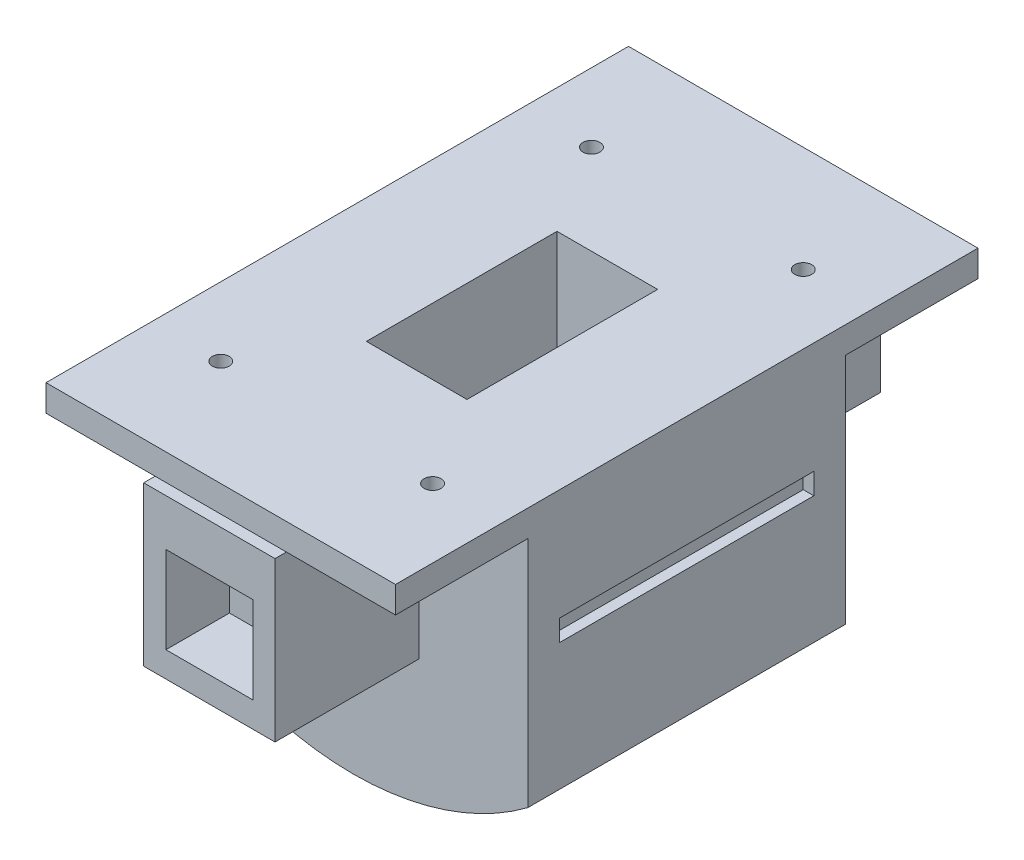
SolidWorks part; units mm, degrees
ref_plane "Front Plane" through (0, 0, 0) normal (0, 0, 1) x (1, 0, 0)
ref_plane "Top Plane" through (0, 0, 0) normal (0, 1, 0) x (1, 0, 0)
ref_plane "Right Plane" through (0, 0, 0) normal (1, 0, 0) x (0, 0, -1)
sketch "Sketch1" plane through (0, 0, 0) normal (0, 0, 1) x (1, 0, 0)
  line L0 (0, 0) -> (0, -42) construction
  line L1 (0, 0) -> (55, 0)
  line L2 (55, 0) -> (-55, 0)
  arc A0 (-55, 0) -> (55, 0) centre (0, 0) ccw
  dimension "D2" = 55
  dimension "D1" = 42
extrude "Boss-Extrude1" add sketch "Sketch1" along normal blind 30 and the other way blind 30 contours L2 A0 L1 region at (0, -23.3427, 0)
sketch "Sketch2" plane through (0, 0, 0) normal (0, 0, 1) x (1, 0, 0)
  line L1 (0, 0) -> (-9.5, 0)
  line L3 (2.8861, -52) -> (-9.5, -52)
  line L4 (-9.5, 0) -> (-9.5, -52)
  line L5 (0, 0) -> (9.5, 0)
  line L7 (2.8861, -52) -> (9.5, -52)
  line L8 (9.5, 0) -> (9.5, -52)
  circle A0 centre (0, 0) radius 42
  dimension "D1" = 84
  dimension "D2" = 9.5
  dimension "D3" = 9.5
  dimension "D4" = 52
extrude "Cut-Extrude1" cut sketch "Sketch2" against normal blind 18 and the other way blind 18 contours L4 A0 L8 L5 L1 | A0 L4 L3 | A0 L3 L7 L8 region at (0, -20.8208, 0) region at (0, -46.8145, 0)
sketch "Sketch3" plane through (0, 0, 30) normal (0, 0, 1) x (1, 0, 0)
  line L0 (0, 0) -> (0, -28.5435) construction
  line L1 (-54.8544, -4) -> (-33, -4)
  line L2 (-54.8544, -4) -> (-54.8544, -49)
  line L3 (-54.8544, -49) -> (-33, -49)
  line L4 (-33, -4) -> (-33, -49)
  line L5 (55, 0) -> (-55, 0) construction
  line L6 (33, -4) -> (33, -49)
  line L7 (54.8544, -49) -> (33, -49)
  line L8 (54.8544, -4) -> (54.8544, -49)
  line L9 (54.8544, -4) -> (33, -4)
  arc A0 (-55, 0) -> (55, 0) centre (0, 0) ccw construction
  dimension "D1" = 4
  dimension "D2" = 33
  dimension "D3" = 45
extrude "Cut-Extrude2" cut sketch "Sketch3" against normal through all
sketch "Sketch4" plane through (0, 0, 0) normal (0, 1, 0) x (1, 0, 0)
  line L0 (55, 30) -> (-55, 30) construction
  line L1 (55, 30) -> (55, -30) construction
  line L2 (0, 0) -> (0, 55.9923) construction
  line L3 (0, 0) -> (36.0907, 0) construction
  circle A0 centre (45, 20) radius 1.6
  circle A1 centre (45, -20) radius 1.6
  circle A2 centre (-45, -20) radius 1.6
  circle A3 centre (-45, 20) radius 1.6
  dimension "D1" = 3.2
  dimension "D2" = 10
  dimension "D3" = 10
extrude "Cut-Extrude3" cut sketch "Sketch4" against normal through all
sketch "Sketch6" plane through (33, 0, 0) normal (1, 0, 0) x (0, 0, -1)
  line L0 (-30, -4) -> (-30, -44) construction
  line L1 (-24, -16) -> (24, -16)
  line L2 (-24, -16) -> (-24, -20)
  line L3 (-24, -20) -> (24, -20)
  line L4 (24, -16) -> (24, -20)
  line L5 (30, -4) -> (30, -44) construction
  line L6 (30, -4) -> (-30, -4) construction
  dimension "D1" = 6
  dimension "D2" = 6
  dimension "D3" = 12
  dimension "D4" = 4
extrude "Cut-Extrude5" cut sketch "Sketch6" against normal blind 2
sketch "Sketch9" plane through (0, 0, 0) normal (0, 1, 0) x (1, 0, 0)
  line L5 (-55, 30) -> (-33, 30)
  line L6 (-55, 30) -> (-55, -30)
  line L7 (-55, -30) -> (-33, -30)
  line L8 (-33, 30) -> (-33, -30)
  line L9 (55, 30) -> (33, 30)
  line L10 (55, 30) -> (55, -30)
  line L11 (55, -30) -> (33, -30)
  line L12 (33, 30) -> (33, -30)
extrude "Cut-Extrude7" cut sketch "Sketch9" against normal through all
sketch "Sketch10" plane through (0, 0, 0) normal (0, 1, 0) x (1, 0, 0)
  line L1 (-33, 30) -> (33, 30)
  line L2 (-33, 30) -> (-33, -30)
  line L3 (-33, -30) -> (33, -30)
  line L4 (33, 30) -> (33, -30)
  line L5 (33, -30) -> (-33, -30)
  line L6 (33, -30) -> (33, -55)
  line L7 (33, -55) -> (-33, -55)
  line L8 (-33, -30) -> (-33, -55)
  line L9 (-33, 30) -> (33, 30)
  line L10 (-33, 30) -> (-33, 55)
  line L11 (-33, 55) -> (33, 55)
  line L12 (33, 30) -> (33, 55)
  line L13 (-9.5, 18) -> (9.5, 18)
  line L14 (-9.5, 18) -> (-9.5, -18)
  line L15 (-9.5, -18) -> (9.5, -18)
  line L16 (9.5, 18) -> (9.5, -18)
  line M3 (-33, 30) -> (-33, -30)
  line M4 (-33, -30) -> (33, -30)
  line M5 (33, -30) -> (33, 30)
  line M6 (33, 30) -> (-33, 30)
  line M7 (9.5, -18) -> (-9.5, -18)
  line M8 (-9.5, -18) -> (-9.5, 18)
  line M9 (-9.5, 18) -> (9.5, 18)
  line M10 (9.5, 18) -> (9.5, -18)
  dimension "D1" = 25
  dimension "D2" = 25
extrude "Boss-Extrude2" add sketch "Sketch10" along normal blind 5 contours L12 L11 L10 M6 | M6 M3 M4 M5 M10 M7 M8 M9 | L8 L7 L6 M4 region at (0, 0, -42.5) region at (0, 0, -29.108) region at (0, 0, 42.5)
sketch "Sketch11" plane through (0, 5, 0) normal (0, 1, 0) x (1, 0, 0)
  line L0 (0, 0) -> (-22.9202, 0) construction
  line L1 (-22.9202, 0) -> (0, 0) construction
  circle A0 centre (-20, 35) radius 1.6
  circle A1 centre (20, 35) radius 1.6
  circle A2 centre (-20, -35) radius 1.6
  circle A3 centre (20, -35) radius 1.6
  dimension "D1" = 3.2
  dimension "D2" = 35
  dimension "D3" = 20
  dimension "D5" = 40
  dimension "D4" = 2
extrude "Cut-Extrude8" cut sketch "Sketch11" against normal through all
sketch "Sketch13" plane through (0, 0, -30) normal (0, 0, -1) x (-1, 0, 0)
  line L0 (33, 0) -> (-33, 0) construction
  line L11 (-18.4, 0) -> (-18.4, 5) construction
  line L12 (-12.4, 0) -> (12.4, 0)
  line L13 (-12.4, 0) -> (-12.4, -30)
  line L14 (-12.4, -30) -> (12.4, -30)
  line L15 (12.4, 0) -> (12.4, -30)
  line L16 (18.4, 5) -> (18.4, 0) construction
  point P0 (0, -17)
  dimension "D5" = 6
  dimension "D6" = 30
  dimension "D7" = 6
extrude "Boss-Extrude3" add sketch "Sketch13" along normal blind 27.15
sketch "Sketch14" plane through (0, 0, -57.15) normal (0, 0, -1) x (-1, 0, 0)
  line L0 (33, -44) -> (33, 0) construction
  line L5 (33, 0) -> (12.4, 0) construction
  line L6 (0, -17) -> (0, 0) construction
  line L7 (-8, -9) -> (8, -9)
  line L8 (-8, -9) -> (-8, -25)
  line L9 (-8, -25) -> (8, -25)
  line L10 (8, -9) -> (8, -25)
  line L11 (-8, -9) -> (8, -25) construction
  line L12 (-8, -25) -> (8, -9) construction
  line L14 (-8.2, -8.8) -> (8.2, -8.8)
  line L15 (-8.2, -8.8) -> (-8.2, -25.2)
  line L16 (-8.2, -25.2) -> (8.2, -25.2)
  line L17 (8.2, -8.8) -> (8.2, -25.2)
  line L18 (-8.2, -8.8) -> (8.2, -25.2) construction
  line L19 (-8.2, -25.2) -> (8.2, -8.8) construction
  point P4 (0, -17)
  dimension "D1" = 16
  dimension "D2" = 9
  dimension "D3" = 16
  dimension "D4" = 25
  dimension "D5" = 17
  dimension "D6" = 0.2
  dimension "D7" = 0.2
extrude "Cut-Extrude9" cut sketch "Sketch14" against normal blind 12 contours L10 L7 L8 L9 | L17 L14 L15 L16 L7 L10 L9 L8 region at (0, -17, -57.15) region at (0, -8.8232, -57.15)
ref_plane "Plane1" through (0, 0, 0) normal (0, 0, -1) x (-1, 0, 0)
mirror "Mirror2" about plane through (0, 0, 0) normal (0, 0, -1) of "Boss-Extrude3"
mirror "Mirror3" about plane through (0, 0, 0) normal (0, 0, -1) of "Cut-Extrude9"
